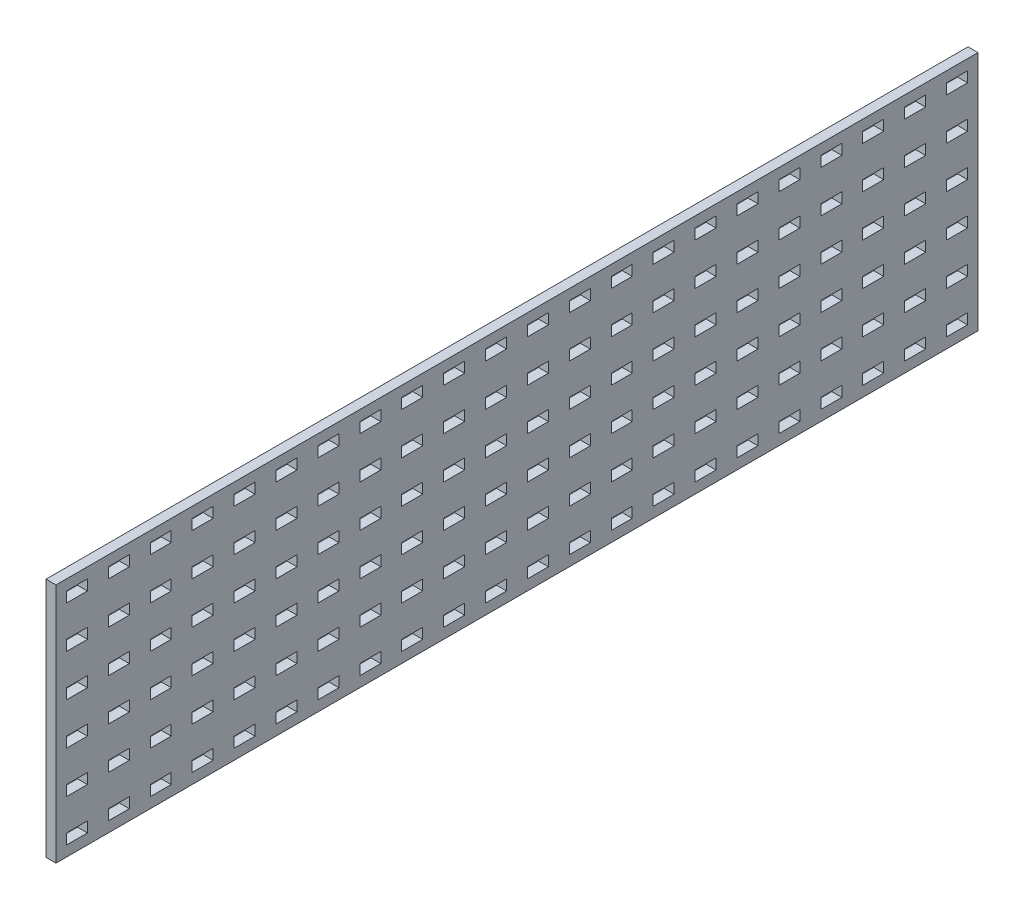
SolidWorks part; units mm, degrees
ref_plane "Front Plane" through (0, 0, 0) normal (0, 0, 1) x (1, 0, 0)
ref_plane "Top Plane" through (0, 0, 0) normal (0, 1, 0) x (1, 0, 0)
ref_plane "Right Plane" through (0, 0, 0) normal (1, 0, 0) x (0, 0, -1)
sketch "Sketch1" plane through (0, 0, 0) normal (1, 0, 0) x (0, 0, -1)
  line L1 (-279.4, -73.025) -> (279.4, -73.025)
  line L2 (-279.4, -73.025) -> (-279.4, 73.025)
  line L3 (-279.4, 73.025) -> (279.4, 73.025)
  line L4 (279.4, -73.025) -> (279.4, 73.025)
  line L5 (-279.4, -73.025) -> (279.4, 73.025) construction
  line L6 (-279.4, 73.025) -> (279.4, -73.025) construction
  point P0 (0, 0)
  dimension "D1" = 558.8
  dimension "D2" = 146.05
extrude "Boss-Extrude1" add sketch "Sketch1" along normal mid plane 6.0452
sketch "Sketch2" plane through (3.0226, 0, 0) normal (1, 0, 0) x (0, 0, -1)
  line L0 (-279.4, -73.025) -> (279.4, -73.025) construction
  line L1 (260.35, -60.325) -> (273.05, -60.325)
  line L2 (260.35, -60.325) -> (260.35, -66.675)
  line L3 (260.35, -66.675) -> (273.05, -66.675)
  line L4 (273.05, -60.325) -> (273.05, -66.675)
  line L5 (260.35, -60.325) -> (273.05, -66.675) construction
  line L6 (260.35, -66.675) -> (273.05, -60.325) construction
  line L7 (279.4, -73.025) -> (279.4, 73.025) construction
  line L8 (234.95, -66.675) -> (247.65, -66.675)
  line L9 (234.95, -60.325) -> (234.95, -66.675)
  line L10 (234.95, -60.325) -> (247.65, -60.325)
  line L11 (247.65, -60.325) -> (247.65, -66.675)
  line L12 (209.55, -66.675) -> (222.25, -66.675)
  line L13 (209.55, -60.325) -> (209.55, -66.675)
  line L14 (209.55, -60.325) -> (222.25, -60.325)
  line L15 (222.25, -60.325) -> (222.25, -66.675)
  line L16 (184.15, -66.675) -> (196.85, -66.675)
  line L17 (184.15, -60.325) -> (184.15, -66.675)
  line L18 (184.15, -60.325) -> (196.85, -60.325)
  line L19 (196.85, -60.325) -> (196.85, -66.675)
  line L20 (158.75, -66.675) -> (171.45, -66.675)
  line L21 (158.75, -60.325) -> (158.75, -66.675)
  line L22 (158.75, -60.325) -> (171.45, -60.325)
  line L23 (171.45, -60.325) -> (171.45, -66.675)
  line L24 (133.35, -66.675) -> (146.05, -66.675)
  line L25 (133.35, -60.325) -> (133.35, -66.675)
  line L26 (133.35, -60.325) -> (146.05, -60.325)
  line L27 (146.05, -60.325) -> (146.05, -66.675)
  line L28 (107.95, -66.675) -> (120.65, -66.675)
  line L29 (107.95, -60.325) -> (107.95, -66.675)
  line L30 (107.95, -60.325) -> (120.65, -60.325)
  line L31 (120.65, -60.325) -> (120.65, -66.675)
  line L32 (82.55, -66.675) -> (95.25, -66.675)
  line L33 (82.55, -60.325) -> (82.55, -66.675)
  line L34 (82.55, -60.325) -> (95.25, -60.325)
  line L35 (95.25, -60.325) -> (95.25, -66.675)
  line L36 (57.15, -66.675) -> (69.85, -66.675)
  line L37 (57.15, -60.325) -> (57.15, -66.675)
  line L38 (57.15, -60.325) -> (69.85, -60.325)
  line L39 (69.85, -60.325) -> (69.85, -66.675)
  line L40 (31.75, -66.675) -> (44.45, -66.675)
  line L41 (31.75, -60.325) -> (31.75, -66.675)
  line L42 (31.75, -60.325) -> (44.45, -60.325)
  line L43 (44.45, -60.325) -> (44.45, -66.675)
  line L44 (6.35, -66.675) -> (19.05, -66.675)
  line L45 (6.35, -60.325) -> (6.35, -66.675)
  line L46 (6.35, -60.325) -> (19.05, -60.325)
  line L47 (19.05, -60.325) -> (19.05, -66.675)
  line L48 (-19.05, -66.675) -> (-6.35, -66.675)
  line L49 (-19.05, -60.325) -> (-19.05, -66.675)
  line L50 (-19.05, -60.325) -> (-6.35, -60.325)
  line L51 (-6.35, -60.325) -> (-6.35, -66.675)
  line L52 (-44.45, -66.675) -> (-31.75, -66.675)
  line L53 (-44.45, -60.325) -> (-44.45, -66.675)
  line L54 (-44.45, -60.325) -> (-31.75, -60.325)
  line L55 (-31.75, -60.325) -> (-31.75, -66.675)
  line L56 (-69.85, -66.675) -> (-57.15, -66.675)
  line L57 (-69.85, -60.325) -> (-69.85, -66.675)
  line L58 (-69.85, -60.325) -> (-57.15, -60.325)
  line L59 (-57.15, -60.325) -> (-57.15, -66.675)
  line L60 (-95.25, -66.675) -> (-82.55, -66.675)
  line L61 (-95.25, -60.325) -> (-95.25, -66.675)
  line L62 (-95.25, -60.325) -> (-82.55, -60.325)
  line L63 (-82.55, -60.325) -> (-82.55, -66.675)
  line L64 (-120.65, -66.675) -> (-107.95, -66.675)
  line L65 (-120.65, -60.325) -> (-120.65, -66.675)
  line L66 (-120.65, -60.325) -> (-107.95, -60.325)
  line L67 (-107.95, -60.325) -> (-107.95, -66.675)
  line L68 (-146.05, -66.675) -> (-133.35, -66.675)
  line L69 (-146.05, -60.325) -> (-146.05, -66.675)
  line L70 (-146.05, -60.325) -> (-133.35, -60.325)
  line L71 (-133.35, -60.325) -> (-133.35, -66.675)
  line L72 (-171.45, -66.675) -> (-158.75, -66.675)
  line L73 (-171.45, -60.325) -> (-171.45, -66.675)
  line L74 (-171.45, -60.325) -> (-158.75, -60.325)
  line L75 (-158.75, -60.325) -> (-158.75, -66.675)
  line L76 (-196.85, -66.675) -> (-184.15, -66.675)
  line L77 (-196.85, -60.325) -> (-196.85, -66.675)
  line L78 (-196.85, -60.325) -> (-184.15, -60.325)
  line L79 (-184.15, -60.325) -> (-184.15, -66.675)
  line L80 (-222.25, -66.675) -> (-209.55, -66.675)
  line L81 (-222.25, -60.325) -> (-222.25, -66.675)
  line L82 (-222.25, -60.325) -> (-209.55, -60.325)
  line L83 (-209.55, -60.325) -> (-209.55, -66.675)
  line L84 (-247.65, -66.675) -> (-234.95, -66.675)
  line L85 (-247.65, -60.325) -> (-247.65, -66.675)
  line L86 (-247.65, -60.325) -> (-234.95, -60.325)
  line L87 (-234.95, -60.325) -> (-234.95, -66.675)
  line L88 (-273.05, -66.675) -> (-260.35, -66.675)
  line L89 (-273.05, -60.325) -> (-273.05, -66.675)
  line L90 (-273.05, -60.325) -> (-260.35, -60.325)
  line L91 (-260.35, -60.325) -> (-260.35, -66.675)
  line L92 (234.95, -41.275) -> (247.65, -41.275)
  line L93 (234.95, -34.925) -> (234.95, -41.275)
  line L94 (234.95, -34.925) -> (247.65, -34.925)
  line L95 (247.65, -34.925) -> (247.65, -41.275)
  line L96 (209.55, -41.275) -> (222.25, -41.275)
  line L97 (209.55, -34.925) -> (209.55, -41.275)
  line L98 (209.55, -34.925) -> (222.25, -34.925)
  line L99 (222.25, -34.925) -> (222.25, -41.275)
  line L100 (184.15, -41.275) -> (196.85, -41.275)
  line L101 (184.15, -34.925) -> (184.15, -41.275)
  line L102 (184.15, -34.925) -> (196.85, -34.925)
  line L103 (196.85, -34.925) -> (196.85, -41.275)
  line L104 (158.75, -41.275) -> (171.45, -41.275)
  line L105 (158.75, -34.925) -> (158.75, -41.275)
  line L106 (158.75, -34.925) -> (171.45, -34.925)
  line L107 (171.45, -34.925) -> (171.45, -41.275)
  line L108 (133.35, -41.275) -> (146.05, -41.275)
  line L109 (133.35, -34.925) -> (133.35, -41.275)
  line L110 (133.35, -34.925) -> (146.05, -34.925)
  line L111 (146.05, -34.925) -> (146.05, -41.275)
  line L112 (107.95, -41.275) -> (120.65, -41.275)
  line L113 (107.95, -34.925) -> (107.95, -41.275)
  line L114 (107.95, -34.925) -> (120.65, -34.925)
  line L115 (120.65, -34.925) -> (120.65, -41.275)
  line L116 (82.55, -41.275) -> (95.25, -41.275)
  line L117 (82.55, -34.925) -> (82.55, -41.275)
  line L118 (82.55, -34.925) -> (95.25, -34.925)
  line L119 (95.25, -34.925) -> (95.25, -41.275)
  line L120 (57.15, -41.275) -> (69.85, -41.275)
  line L121 (57.15, -34.925) -> (57.15, -41.275)
  line L122 (57.15, -34.925) -> (69.85, -34.925)
  line L123 (69.85, -34.925) -> (69.85, -41.275)
  line L124 (31.75, -41.275) -> (44.45, -41.275)
  line L125 (31.75, -34.925) -> (31.75, -41.275)
  line L126 (31.75, -34.925) -> (44.45, -34.925)
  line L127 (44.45, -34.925) -> (44.45, -41.275)
  line L128 (6.35, -41.275) -> (19.05, -41.275)
  line L129 (6.35, -34.925) -> (6.35, -41.275)
  line L130 (6.35, -34.925) -> (19.05, -34.925)
  line L131 (19.05, -34.925) -> (19.05, -41.275)
  line L132 (-19.05, -41.275) -> (-6.35, -41.275)
  line L133 (-19.05, -34.925) -> (-19.05, -41.275)
  line L134 (-19.05, -34.925) -> (-6.35, -34.925)
  line L135 (-6.35, -34.925) -> (-6.35, -41.275)
  line L136 (-44.45, -41.275) -> (-31.75, -41.275)
  line L137 (-44.45, -34.925) -> (-44.45, -41.275)
  line L138 (-44.45, -34.925) -> (-31.75, -34.925)
  line L139 (-31.75, -34.925) -> (-31.75, -41.275)
  line L140 (-69.85, -41.275) -> (-57.15, -41.275)
  line L141 (-69.85, -34.925) -> (-69.85, -41.275)
  line L142 (-69.85, -34.925) -> (-57.15, -34.925)
  line L143 (-57.15, -34.925) -> (-57.15, -41.275)
  line L144 (-95.25, -41.275) -> (-82.55, -41.275)
  line L145 (-95.25, -34.925) -> (-95.25, -41.275)
  line L146 (-95.25, -34.925) -> (-82.55, -34.925)
  line L147 (-82.55, -34.925) -> (-82.55, -41.275)
  line L148 (-120.65, -41.275) -> (-107.95, -41.275)
  line L149 (-120.65, -34.925) -> (-120.65, -41.275)
  line L150 (-120.65, -34.925) -> (-107.95, -34.925)
  line L151 (-107.95, -34.925) -> (-107.95, -41.275)
  line L152 (-146.05, -41.275) -> (-133.35, -41.275)
  line L153 (-146.05, -34.925) -> (-146.05, -41.275)
  line L154 (-146.05, -34.925) -> (-133.35, -34.925)
  line L155 (-133.35, -34.925) -> (-133.35, -41.275)
  line L156 (-171.45, -41.275) -> (-158.75, -41.275)
  line L157 (-171.45, -34.925) -> (-171.45, -41.275)
  line L158 (-171.45, -34.925) -> (-158.75, -34.925)
  line L159 (-158.75, -34.925) -> (-158.75, -41.275)
  line L160 (-196.85, -41.275) -> (-184.15, -41.275)
  line L161 (-196.85, -34.925) -> (-196.85, -41.275)
  line L162 (-196.85, -34.925) -> (-184.15, -34.925)
  line L163 (-184.15, -34.925) -> (-184.15, -41.275)
  line L164 (-222.25, -41.275) -> (-209.55, -41.275)
  line L165 (-222.25, -34.925) -> (-222.25, -41.275)
  line L166 (-222.25, -34.925) -> (-209.55, -34.925)
  line L167 (-209.55, -34.925) -> (-209.55, -41.275)
  line L168 (-247.65, -41.275) -> (-234.95, -41.275)
  line L169 (-247.65, -34.925) -> (-247.65, -41.275)
  line L170 (-247.65, -34.925) -> (-234.95, -34.925)
  line L171 (-234.95, -34.925) -> (-234.95, -41.275)
  line L172 (-273.05, -41.275) -> (-260.35, -41.275)
  line L173 (-273.05, -34.925) -> (-273.05, -41.275)
  line L174 (-273.05, -34.925) -> (-260.35, -34.925)
  line L175 (-260.35, -34.925) -> (-260.35, -41.275)
  line L176 (234.95, -15.875) -> (247.65, -15.875)
  line L177 (234.95, -9.525) -> (234.95, -15.875)
  line L178 (234.95, -9.525) -> (247.65, -9.525)
  line L179 (247.65, -9.525) -> (247.65, -15.875)
  line L180 (209.55, -15.875) -> (222.25, -15.875)
  line L181 (209.55, -9.525) -> (209.55, -15.875)
  line L182 (209.55, -9.525) -> (222.25, -9.525)
  line L183 (222.25, -9.525) -> (222.25, -15.875)
  line L184 (184.15, -15.875) -> (196.85, -15.875)
  line L185 (184.15, -9.525) -> (184.15, -15.875)
  line L186 (184.15, -9.525) -> (196.85, -9.525)
  line L187 (196.85, -9.525) -> (196.85, -15.875)
  line L188 (158.75, -15.875) -> (171.45, -15.875)
  line L189 (158.75, -9.525) -> (158.75, -15.875)
  line L190 (158.75, -9.525) -> (171.45, -9.525)
  line L191 (171.45, -9.525) -> (171.45, -15.875)
  line L192 (133.35, -15.875) -> (146.05, -15.875)
  line L193 (133.35, -9.525) -> (133.35, -15.875)
  line L194 (133.35, -9.525) -> (146.05, -9.525)
  line L195 (146.05, -9.525) -> (146.05, -15.875)
  line L196 (107.95, -15.875) -> (120.65, -15.875)
  line L197 (107.95, -9.525) -> (107.95, -15.875)
  line L198 (107.95, -9.525) -> (120.65, -9.525)
  line L199 (120.65, -9.525) -> (120.65, -15.875)
  line L200 (82.55, -15.875) -> (95.25, -15.875)
  line L201 (82.55, -9.525) -> (82.55, -15.875)
  line L202 (82.55, -9.525) -> (95.25, -9.525)
  line L203 (95.25, -9.525) -> (95.25, -15.875)
  line L204 (57.15, -15.875) -> (69.85, -15.875)
  line L205 (57.15, -9.525) -> (57.15, -15.875)
  line L206 (57.15, -9.525) -> (69.85, -9.525)
  line L207 (69.85, -9.525) -> (69.85, -15.875)
  line L208 (31.75, -15.875) -> (44.45, -15.875)
  line L209 (31.75, -9.525) -> (31.75, -15.875)
  line L210 (31.75, -9.525) -> (44.45, -9.525)
  line L211 (44.45, -9.525) -> (44.45, -15.875)
  line L212 (6.35, -15.875) -> (19.05, -15.875)
  line L213 (6.35, -9.525) -> (6.35, -15.875)
  line L214 (6.35, -9.525) -> (19.05, -9.525)
  line L215 (19.05, -9.525) -> (19.05, -15.875)
  line L216 (-19.05, -15.875) -> (-6.35, -15.875)
  line L217 (-19.05, -9.525) -> (-19.05, -15.875)
  line L218 (-19.05, -9.525) -> (-6.35, -9.525)
  line L219 (-6.35, -9.525) -> (-6.35, -15.875)
  line L220 (-44.45, -15.875) -> (-31.75, -15.875)
  line L221 (-44.45, -9.525) -> (-44.45, -15.875)
  line L222 (-44.45, -9.525) -> (-31.75, -9.525)
  line L223 (-31.75, -9.525) -> (-31.75, -15.875)
  line L224 (-69.85, -15.875) -> (-57.15, -15.875)
  line L225 (-69.85, -9.525) -> (-69.85, -15.875)
  line L226 (-69.85, -9.525) -> (-57.15, -9.525)
  line L227 (-57.15, -9.525) -> (-57.15, -15.875)
  line L228 (-95.25, -15.875) -> (-82.55, -15.875)
  line L229 (-95.25, -9.525) -> (-95.25, -15.875)
  line L230 (-95.25, -9.525) -> (-82.55, -9.525)
  line L231 (-82.55, -9.525) -> (-82.55, -15.875)
  line L232 (-120.65, -15.875) -> (-107.95, -15.875)
  line L233 (-120.65, -9.525) -> (-120.65, -15.875)
  line L234 (-120.65, -9.525) -> (-107.95, -9.525)
  line L235 (-107.95, -9.525) -> (-107.95, -15.875)
  line L236 (-146.05, -15.875) -> (-133.35, -15.875)
  line L237 (-146.05, -9.525) -> (-146.05, -15.875)
  line L238 (-146.05, -9.525) -> (-133.35, -9.525)
  line L239 (-133.35, -9.525) -> (-133.35, -15.875)
  line L240 (-171.45, -15.875) -> (-158.75, -15.875)
  line L241 (-171.45, -9.525) -> (-171.45, -15.875)
  line L242 (-171.45, -9.525) -> (-158.75, -9.525)
  line L243 (-158.75, -9.525) -> (-158.75, -15.875)
  line L244 (-196.85, -15.875) -> (-184.15, -15.875)
  line L245 (-196.85, -9.525) -> (-196.85, -15.875)
  line L246 (-196.85, -9.525) -> (-184.15, -9.525)
  line L247 (-184.15, -9.525) -> (-184.15, -15.875)
  line L248 (-222.25, -15.875) -> (-209.55, -15.875)
  line L249 (-222.25, -9.525) -> (-222.25, -15.875)
  line L250 (-222.25, -9.525) -> (-209.55, -9.525)
  line L251 (-209.55, -9.525) -> (-209.55, -15.875)
  line L252 (-247.65, -15.875) -> (-234.95, -15.875)
  line L253 (-247.65, -9.525) -> (-247.65, -15.875)
  line L254 (-247.65, -9.525) -> (-234.95, -9.525)
  line L255 (-234.95, -9.525) -> (-234.95, -15.875)
  line L256 (-273.05, -15.875) -> (-260.35, -15.875)
  line L257 (-273.05, -9.525) -> (-273.05, -15.875)
  line L258 (-273.05, -9.525) -> (-260.35, -9.525)
  line L259 (-260.35, -9.525) -> (-260.35, -15.875)
  line L260 (234.95, 9.525) -> (247.65, 9.525)
  line L261 (234.95, 15.875) -> (234.95, 9.525)
  line L262 (234.95, 15.875) -> (247.65, 15.875)
  line L263 (247.65, 15.875) -> (247.65, 9.525)
  line L264 (209.55, 9.525) -> (222.25, 9.525)
  line L265 (209.55, 15.875) -> (209.55, 9.525)
  line L266 (209.55, 15.875) -> (222.25, 15.875)
  line L267 (222.25, 15.875) -> (222.25, 9.525)
  line L268 (184.15, 9.525) -> (196.85, 9.525)
  line L269 (184.15, 15.875) -> (184.15, 9.525)
  line L270 (184.15, 15.875) -> (196.85, 15.875)
  line L271 (196.85, 15.875) -> (196.85, 9.525)
  line L272 (158.75, 9.525) -> (171.45, 9.525)
  line L273 (158.75, 15.875) -> (158.75, 9.525)
  line L274 (158.75, 15.875) -> (171.45, 15.875)
  line L275 (171.45, 15.875) -> (171.45, 9.525)
  line L276 (133.35, 9.525) -> (146.05, 9.525)
  line L277 (133.35, 15.875) -> (133.35, 9.525)
  line L278 (133.35, 15.875) -> (146.05, 15.875)
  line L279 (146.05, 15.875) -> (146.05, 9.525)
  line L280 (107.95, 9.525) -> (120.65, 9.525)
  line L281 (107.95, 15.875) -> (107.95, 9.525)
  line L282 (107.95, 15.875) -> (120.65, 15.875)
  line L283 (120.65, 15.875) -> (120.65, 9.525)
  line L284 (82.55, 9.525) -> (95.25, 9.525)
  line L285 (82.55, 15.875) -> (82.55, 9.525)
  line L286 (82.55, 15.875) -> (95.25, 15.875)
  line L287 (95.25, 15.875) -> (95.25, 9.525)
  line L288 (57.15, 9.525) -> (69.85, 9.525)
  line L289 (57.15, 15.875) -> (57.15, 9.525)
  line L290 (57.15, 15.875) -> (69.85, 15.875)
  line L291 (69.85, 15.875) -> (69.85, 9.525)
  line L292 (31.75, 9.525) -> (44.45, 9.525)
  line L293 (31.75, 15.875) -> (31.75, 9.525)
  line L294 (31.75, 15.875) -> (44.45, 15.875)
  line L295 (44.45, 15.875) -> (44.45, 9.525)
  line L296 (6.35, 9.525) -> (19.05, 9.525)
  line L297 (6.35, 15.875) -> (6.35, 9.525)
  line L298 (6.35, 15.875) -> (19.05, 15.875)
  line L299 (19.05, 15.875) -> (19.05, 9.525)
  line L300 (-19.05, 9.525) -> (-6.35, 9.525)
  line L301 (-19.05, 15.875) -> (-19.05, 9.525)
  line L302 (-19.05, 15.875) -> (-6.35, 15.875)
  line L303 (-6.35, 15.875) -> (-6.35, 9.525)
  line L304 (-44.45, 9.525) -> (-31.75, 9.525)
  line L305 (-44.45, 15.875) -> (-44.45, 9.525)
  line L306 (-44.45, 15.875) -> (-31.75, 15.875)
  line L307 (-31.75, 15.875) -> (-31.75, 9.525)
  line L308 (-69.85, 9.525) -> (-57.15, 9.525)
  line L309 (-69.85, 15.875) -> (-69.85, 9.525)
  line L310 (-69.85, 15.875) -> (-57.15, 15.875)
  line L311 (-57.15, 15.875) -> (-57.15, 9.525)
  line L312 (-95.25, 9.525) -> (-82.55, 9.525)
  line L313 (-95.25, 15.875) -> (-95.25, 9.525)
  line L314 (-95.25, 15.875) -> (-82.55, 15.875)
  line L315 (-82.55, 15.875) -> (-82.55, 9.525)
  line L316 (-120.65, 9.525) -> (-107.95, 9.525)
  line L317 (-120.65, 15.875) -> (-120.65, 9.525)
  line L318 (-120.65, 15.875) -> (-107.95, 15.875)
  line L319 (-107.95, 15.875) -> (-107.95, 9.525)
  line L320 (-146.05, 9.525) -> (-133.35, 9.525)
  line L321 (-146.05, 15.875) -> (-146.05, 9.525)
  line L322 (-146.05, 15.875) -> (-133.35, 15.875)
  line L323 (-133.35, 15.875) -> (-133.35, 9.525)
  line L324 (-171.45, 9.525) -> (-158.75, 9.525)
  line L325 (-171.45, 15.875) -> (-171.45, 9.525)
  line L326 (-171.45, 15.875) -> (-158.75, 15.875)
  line L327 (-158.75, 15.875) -> (-158.75, 9.525)
  line L328 (-196.85, 9.525) -> (-184.15, 9.525)
  line L329 (-196.85, 15.875) -> (-196.85, 9.525)
  line L330 (-196.85, 15.875) -> (-184.15, 15.875)
  line L331 (-184.15, 15.875) -> (-184.15, 9.525)
  line L332 (-222.25, 9.525) -> (-209.55, 9.525)
  line L333 (-222.25, 15.875) -> (-222.25, 9.525)
  line L334 (-222.25, 15.875) -> (-209.55, 15.875)
  line L335 (-209.55, 15.875) -> (-209.55, 9.525)
  line L336 (-247.65, 9.525) -> (-234.95, 9.525)
  line L337 (-247.65, 15.875) -> (-247.65, 9.525)
  line L338 (-247.65, 15.875) -> (-234.95, 15.875)
  line L339 (-234.95, 15.875) -> (-234.95, 9.525)
  line L340 (-273.05, 9.525) -> (-260.35, 9.525)
  line L341 (-273.05, 15.875) -> (-273.05, 9.525)
  line L342 (-273.05, 15.875) -> (-260.35, 15.875)
  line L343 (-260.35, 15.875) -> (-260.35, 9.525)
  line L344 (234.95, 34.925) -> (247.65, 34.925)
  line L345 (234.95, 41.275) -> (234.95, 34.925)
  line L346 (234.95, 41.275) -> (247.65, 41.275)
  line L347 (247.65, 41.275) -> (247.65, 34.925)
  line L348 (209.55, 34.925) -> (222.25, 34.925)
  line L349 (209.55, 41.275) -> (209.55, 34.925)
  line L350 (209.55, 41.275) -> (222.25, 41.275)
  line L351 (222.25, 41.275) -> (222.25, 34.925)
  line L352 (184.15, 34.925) -> (196.85, 34.925)
  line L353 (184.15, 41.275) -> (184.15, 34.925)
  line L354 (184.15, 41.275) -> (196.85, 41.275)
  line L355 (196.85, 41.275) -> (196.85, 34.925)
  line L356 (158.75, 34.925) -> (171.45, 34.925)
  line L357 (158.75, 41.275) -> (158.75, 34.925)
  line L358 (158.75, 41.275) -> (171.45, 41.275)
  line L359 (171.45, 41.275) -> (171.45, 34.925)
  line L360 (133.35, 34.925) -> (146.05, 34.925)
  line L361 (133.35, 41.275) -> (133.35, 34.925)
  line L362 (133.35, 41.275) -> (146.05, 41.275)
  line L363 (146.05, 41.275) -> (146.05, 34.925)
  line L364 (107.95, 34.925) -> (120.65, 34.925)
  line L365 (107.95, 41.275) -> (107.95, 34.925)
  line L366 (107.95, 41.275) -> (120.65, 41.275)
  line L367 (120.65, 41.275) -> (120.65, 34.925)
  line L368 (82.55, 34.925) -> (95.25, 34.925)
  line L369 (82.55, 41.275) -> (82.55, 34.925)
  line L370 (82.55, 41.275) -> (95.25, 41.275)
  line L371 (95.25, 41.275) -> (95.25, 34.925)
  line L372 (57.15, 34.925) -> (69.85, 34.925)
  line L373 (57.15, 41.275) -> (57.15, 34.925)
  line L374 (57.15, 41.275) -> (69.85, 41.275)
  line L375 (69.85, 41.275) -> (69.85, 34.925)
  line L376 (31.75, 34.925) -> (44.45, 34.925)
  line L377 (31.75, 41.275) -> (31.75, 34.925)
  line L378 (31.75, 41.275) -> (44.45, 41.275)
  line L379 (44.45, 41.275) -> (44.45, 34.925)
  line L380 (6.35, 34.925) -> (19.05, 34.925)
  line L381 (6.35, 41.275) -> (6.35, 34.925)
  line L382 (6.35, 41.275) -> (19.05, 41.275)
  line L383 (19.05, 41.275) -> (19.05, 34.925)
  line L384 (-19.05, 34.925) -> (-6.35, 34.925)
  line L385 (-19.05, 41.275) -> (-19.05, 34.925)
  line L386 (-19.05, 41.275) -> (-6.35, 41.275)
  line L387 (-6.35, 41.275) -> (-6.35, 34.925)
  line L388 (-44.45, 34.925) -> (-31.75, 34.925)
  line L389 (-44.45, 41.275) -> (-44.45, 34.925)
  line L390 (-44.45, 41.275) -> (-31.75, 41.275)
  line L391 (-31.75, 41.275) -> (-31.75, 34.925)
  line L392 (-69.85, 34.925) -> (-57.15, 34.925)
  line L393 (-69.85, 41.275) -> (-69.85, 34.925)
  line L394 (-69.85, 41.275) -> (-57.15, 41.275)
  line L395 (-57.15, 41.275) -> (-57.15, 34.925)
  line L396 (-95.25, 34.925) -> (-82.55, 34.925)
  line L397 (-95.25, 41.275) -> (-95.25, 34.925)
  line L398 (-95.25, 41.275) -> (-82.55, 41.275)
  line L399 (-82.55, 41.275) -> (-82.55, 34.925)
  line L400 (-120.65, 34.925) -> (-107.95, 34.925)
  line L401 (-120.65, 41.275) -> (-120.65, 34.925)
  line L402 (-120.65, 41.275) -> (-107.95, 41.275)
  line L403 (-107.95, 41.275) -> (-107.95, 34.925)
  line L404 (-146.05, 34.925) -> (-133.35, 34.925)
  line L405 (-146.05, 41.275) -> (-146.05, 34.925)
  line L406 (-146.05, 41.275) -> (-133.35, 41.275)
  line L407 (-133.35, 41.275) -> (-133.35, 34.925)
  line L408 (-171.45, 34.925) -> (-158.75, 34.925)
  line L409 (-171.45, 41.275) -> (-171.45, 34.925)
  line L410 (-171.45, 41.275) -> (-158.75, 41.275)
  line L411 (-158.75, 41.275) -> (-158.75, 34.925)
  line L412 (-196.85, 34.925) -> (-184.15, 34.925)
  line L413 (-196.85, 41.275) -> (-196.85, 34.925)
  line L414 (-196.85, 41.275) -> (-184.15, 41.275)
  line L415 (-184.15, 41.275) -> (-184.15, 34.925)
  line L416 (-222.25, 34.925) -> (-209.55, 34.925)
  line L417 (-222.25, 41.275) -> (-222.25, 34.925)
  line L418 (-222.25, 41.275) -> (-209.55, 41.275)
  line L419 (-209.55, 41.275) -> (-209.55, 34.925)
  line L420 (-247.65, 34.925) -> (-234.95, 34.925)
  line L421 (-247.65, 41.275) -> (-247.65, 34.925)
  line L422 (-247.65, 41.275) -> (-234.95, 41.275)
  line L423 (-234.95, 41.275) -> (-234.95, 34.925)
  line L424 (-273.05, 34.925) -> (-260.35, 34.925)
  line L425 (-273.05, 41.275) -> (-273.05, 34.925)
  line L426 (-273.05, 41.275) -> (-260.35, 41.275)
  line L427 (-260.35, 41.275) -> (-260.35, 34.925)
  line L428 (234.95, 60.325) -> (247.65, 60.325)
  line L429 (234.95, 66.675) -> (234.95, 60.325)
  line L430 (234.95, 66.675) -> (247.65, 66.675)
  line L431 (247.65, 66.675) -> (247.65, 60.325)
  line L432 (209.55, 60.325) -> (222.25, 60.325)
  line L433 (209.55, 66.675) -> (209.55, 60.325)
  line L434 (209.55, 66.675) -> (222.25, 66.675)
  line L435 (222.25, 66.675) -> (222.25, 60.325)
  line L436 (184.15, 60.325) -> (196.85, 60.325)
  line L437 (184.15, 66.675) -> (184.15, 60.325)
  line L438 (184.15, 66.675) -> (196.85, 66.675)
  line L439 (196.85, 66.675) -> (196.85, 60.325)
  line L440 (158.75, 60.325) -> (171.45, 60.325)
  line L441 (158.75, 66.675) -> (158.75, 60.325)
  line L442 (158.75, 66.675) -> (171.45, 66.675)
  line L443 (171.45, 66.675) -> (171.45, 60.325)
  line L444 (133.35, 60.325) -> (146.05, 60.325)
  line L445 (133.35, 66.675) -> (133.35, 60.325)
  line L446 (133.35, 66.675) -> (146.05, 66.675)
  line L447 (146.05, 66.675) -> (146.05, 60.325)
  line L448 (107.95, 60.325) -> (120.65, 60.325)
  line L449 (107.95, 66.675) -> (107.95, 60.325)
  line L450 (107.95, 66.675) -> (120.65, 66.675)
  line L451 (120.65, 66.675) -> (120.65, 60.325)
  line L452 (82.55, 60.325) -> (95.25, 60.325)
  line L453 (82.55, 66.675) -> (82.55, 60.325)
  line L454 (82.55, 66.675) -> (95.25, 66.675)
  line L455 (95.25, 66.675) -> (95.25, 60.325)
  line L456 (57.15, 60.325) -> (69.85, 60.325)
  line L457 (57.15, 66.675) -> (57.15, 60.325)
  line L458 (57.15, 66.675) -> (69.85, 66.675)
  line L459 (69.85, 66.675) -> (69.85, 60.325)
  line L460 (31.75, 60.325) -> (44.45, 60.325)
  line L461 (31.75, 66.675) -> (31.75, 60.325)
  line L462 (31.75, 66.675) -> (44.45, 66.675)
  line L463 (44.45, 66.675) -> (44.45, 60.325)
  line L464 (6.35, 60.325) -> (19.05, 60.325)
  line L465 (6.35, 66.675) -> (6.35, 60.325)
  line L466 (6.35, 66.675) -> (19.05, 66.675)
  line L467 (19.05, 66.675) -> (19.05, 60.325)
  line L468 (-19.05, 60.325) -> (-6.35, 60.325)
  line L469 (-19.05, 66.675) -> (-19.05, 60.325)
  line L470 (-19.05, 66.675) -> (-6.35, 66.675)
  line L471 (-6.35, 66.675) -> (-6.35, 60.325)
  line L472 (-44.45, 60.325) -> (-31.75, 60.325)
  line L473 (-44.45, 66.675) -> (-44.45, 60.325)
  line L474 (-44.45, 66.675) -> (-31.75, 66.675)
  line L475 (-31.75, 66.675) -> (-31.75, 60.325)
  line L476 (-69.85, 60.325) -> (-57.15, 60.325)
  line L477 (-69.85, 66.675) -> (-69.85, 60.325)
  line L478 (-69.85, 66.675) -> (-57.15, 66.675)
  line L479 (-57.15, 66.675) -> (-57.15, 60.325)
  line L480 (-95.25, 60.325) -> (-82.55, 60.325)
  line L481 (-95.25, 66.675) -> (-95.25, 60.325)
  line L482 (-95.25, 66.675) -> (-82.55, 66.675)
  line L483 (-82.55, 66.675) -> (-82.55, 60.325)
  line L484 (-120.65, 60.325) -> (-107.95, 60.325)
  line L485 (-120.65, 66.675) -> (-120.65, 60.325)
  line L486 (-120.65, 66.675) -> (-107.95, 66.675)
  line L487 (-107.95, 66.675) -> (-107.95, 60.325)
  line L488 (-146.05, 60.325) -> (-133.35, 60.325)
  line L489 (-146.05, 66.675) -> (-146.05, 60.325)
  line L490 (-146.05, 66.675) -> (-133.35, 66.675)
  line L491 (-133.35, 66.675) -> (-133.35, 60.325)
  line L492 (-171.45, 60.325) -> (-158.75, 60.325)
  line L493 (-171.45, 66.675) -> (-171.45, 60.325)
  line L494 (-171.45, 66.675) -> (-158.75, 66.675)
  line L495 (-158.75, 66.675) -> (-158.75, 60.325)
  line L496 (-196.85, 60.325) -> (-184.15, 60.325)
  line L497 (-196.85, 66.675) -> (-196.85, 60.325)
  line L498 (-196.85, 66.675) -> (-184.15, 66.675)
  line L499 (-184.15, 66.675) -> (-184.15, 60.325)
  line L500 (-222.25, 60.325) -> (-209.55, 60.325)
  line L501 (-222.25, 66.675) -> (-222.25, 60.325)
  line L502 (-222.25, 66.675) -> (-209.55, 66.675)
  line L503 (-209.55, 66.675) -> (-209.55, 60.325)
  line L504 (-247.65, 60.325) -> (-234.95, 60.325)
  line L505 (-247.65, 66.675) -> (-247.65, 60.325)
  line L506 (-247.65, 66.675) -> (-234.95, 66.675)
  line L507 (-234.95, 66.675) -> (-234.95, 60.325)
  line L508 (-273.05, 60.325) -> (-260.35, 60.325)
  line L509 (-273.05, 66.675) -> (-273.05, 60.325)
  line L510 (-273.05, 66.675) -> (-260.35, 66.675)
  line L511 (-260.35, 66.675) -> (-260.35, 60.325)
  line L512 (234.95, 85.725) -> (247.65, 85.725)
  line L513 (234.95, 92.075) -> (234.95, 85.725)
  line L514 (234.95, 92.075) -> (247.65, 92.075)
  line L515 (247.65, 92.075) -> (247.65, 85.725)
  line L516 (209.55, 85.725) -> (222.25, 85.725)
  line L517 (209.55, 92.075) -> (209.55, 85.725)
  line L518 (209.55, 92.075) -> (222.25, 92.075)
  line L519 (222.25, 92.075) -> (222.25, 85.725)
  line L520 (184.15, 85.725) -> (196.85, 85.725)
  line L521 (184.15, 92.075) -> (184.15, 85.725)
  line L522 (184.15, 92.075) -> (196.85, 92.075)
  line L523 (196.85, 92.075) -> (196.85, 85.725)
  line L524 (158.75, 85.725) -> (171.45, 85.725)
  line L525 (158.75, 92.075) -> (158.75, 85.725)
  line L526 (158.75, 92.075) -> (171.45, 92.075)
  line L527 (171.45, 92.075) -> (171.45, 85.725)
  line L528 (133.35, 85.725) -> (146.05, 85.725)
  line L529 (133.35, 92.075) -> (133.35, 85.725)
  line L530 (133.35, 92.075) -> (146.05, 92.075)
  line L531 (146.05, 92.075) -> (146.05, 85.725)
  line L532 (107.95, 85.725) -> (120.65, 85.725)
  line L533 (107.95, 92.075) -> (107.95, 85.725)
  line L534 (107.95, 92.075) -> (120.65, 92.075)
  line L535 (120.65, 92.075) -> (120.65, 85.725)
  line L536 (82.55, 85.725) -> (95.25, 85.725)
  line L537 (82.55, 92.075) -> (82.55, 85.725)
  line L538 (82.55, 92.075) -> (95.25, 92.075)
  line L539 (95.25, 92.075) -> (95.25, 85.725)
  line L540 (57.15, 85.725) -> (69.85, 85.725)
  line L541 (57.15, 92.075) -> (57.15, 85.725)
  line L542 (57.15, 92.075) -> (69.85, 92.075)
  line L543 (69.85, 92.075) -> (69.85, 85.725)
  line L544 (31.75, 85.725) -> (44.45, 85.725)
  line L545 (31.75, 92.075) -> (31.75, 85.725)
  line L546 (31.75, 92.075) -> (44.45, 92.075)
  line L547 (44.45, 92.075) -> (44.45, 85.725)
  line L548 (6.35, 85.725) -> (19.05, 85.725)
  line L549 (6.35, 92.075) -> (6.35, 85.725)
  line L550 (6.35, 92.075) -> (19.05, 92.075)
  line L551 (19.05, 92.075) -> (19.05, 85.725)
  line L552 (-19.05, 85.725) -> (-6.35, 85.725)
  line L553 (-19.05, 92.075) -> (-19.05, 85.725)
  line L554 (-19.05, 92.075) -> (-6.35, 92.075)
  line L555 (-6.35, 92.075) -> (-6.35, 85.725)
  line L556 (-44.45, 85.725) -> (-31.75, 85.725)
  line L557 (-44.45, 92.075) -> (-44.45, 85.725)
  line L558 (-44.45, 92.075) -> (-31.75, 92.075)
  line L559 (-31.75, 92.075) -> (-31.75, 85.725)
  line L560 (-69.85, 85.725) -> (-57.15, 85.725)
  line L561 (-69.85, 92.075) -> (-69.85, 85.725)
  line L562 (-69.85, 92.075) -> (-57.15, 92.075)
  line L563 (-57.15, 92.075) -> (-57.15, 85.725)
  line L564 (-95.25, 85.725) -> (-82.55, 85.725)
  line L565 (-95.25, 92.075) -> (-95.25, 85.725)
  line L566 (-95.25, 92.075) -> (-82.55, 92.075)
  line L567 (-82.55, 92.075) -> (-82.55, 85.725)
  line L568 (-120.65, 85.725) -> (-107.95, 85.725)
  line L569 (-120.65, 92.075) -> (-120.65, 85.725)
  line L570 (-120.65, 92.075) -> (-107.95, 92.075)
  line L571 (-107.95, 92.075) -> (-107.95, 85.725)
  line L572 (-146.05, 85.725) -> (-133.35, 85.725)
  line L573 (-146.05, 92.075) -> (-146.05, 85.725)
  line L574 (-146.05, 92.075) -> (-133.35, 92.075)
  line L575 (-133.35, 92.075) -> (-133.35, 85.725)
  line L576 (-171.45, 85.725) -> (-158.75, 85.725)
  line L577 (-171.45, 92.075) -> (-171.45, 85.725)
  line L578 (-171.45, 92.075) -> (-158.75, 92.075)
  line L579 (-158.75, 92.075) -> (-158.75, 85.725)
  line L580 (-196.85, 85.725) -> (-184.15, 85.725)
  line L581 (-196.85, 92.075) -> (-196.85, 85.725)
  line L582 (-196.85, 92.075) -> (-184.15, 92.075)
  line L583 (-184.15, 92.075) -> (-184.15, 85.725)
  line L584 (-222.25, 85.725) -> (-209.55, 85.725)
  line L585 (-222.25, 92.075) -> (-222.25, 85.725)
  line L586 (-222.25, 92.075) -> (-209.55, 92.075)
  line L587 (-209.55, 92.075) -> (-209.55, 85.725)
  line L588 (-247.65, 85.725) -> (-234.95, 85.725)
  line L589 (-247.65, 92.075) -> (-247.65, 85.725)
  line L590 (-247.65, 92.075) -> (-234.95, 92.075)
  line L591 (-234.95, 92.075) -> (-234.95, 85.725)
  line L592 (-273.05, 85.725) -> (-260.35, 85.725)
  line L593 (-273.05, 92.075) -> (-273.05, 85.725)
  line L594 (-273.05, 92.075) -> (-260.35, 92.075)
  line L595 (-260.35, 92.075) -> (-260.35, 85.725)
  line L596 (234.95, 111.125) -> (247.65, 111.125)
  line L597 (234.95, 117.475) -> (234.95, 111.125)
  line L598 (234.95, 117.475) -> (247.65, 117.475)
  line L599 (247.65, 117.475) -> (247.65, 111.125)
  line L600 (209.55, 111.125) -> (222.25, 111.125)
  line L601 (209.55, 117.475) -> (209.55, 111.125)
  line L602 (209.55, 117.475) -> (222.25, 117.475)
  line L603 (222.25, 117.475) -> (222.25, 111.125)
  line L604 (184.15, 111.125) -> (196.85, 111.125)
  line L605 (184.15, 117.475) -> (184.15, 111.125)
  line L606 (184.15, 117.475) -> (196.85, 117.475)
  line L607 (196.85, 117.475) -> (196.85, 111.125)
  line L608 (158.75, 111.125) -> (171.45, 111.125)
  line L609 (158.75, 117.475) -> (158.75, 111.125)
  line L610 (158.75, 117.475) -> (171.45, 117.475)
  line L611 (171.45, 117.475) -> (171.45, 111.125)
  line L612 (133.35, 111.125) -> (146.05, 111.125)
  line L613 (133.35, 117.475) -> (133.35, 111.125)
  line L614 (133.35, 117.475) -> (146.05, 117.475)
  line L615 (146.05, 117.475) -> (146.05, 111.125)
  line L616 (107.95, 111.125) -> (120.65, 111.125)
  line L617 (107.95, 117.475) -> (107.95, 111.125)
  line L618 (107.95, 117.475) -> (120.65, 117.475)
  line L619 (120.65, 117.475) -> (120.65, 111.125)
  line L620 (82.55, 111.125) -> (95.25, 111.125)
  line L621 (82.55, 117.475) -> (82.55, 111.125)
  line L622 (82.55, 117.475) -> (95.25, 117.475)
  line L623 (95.25, 117.475) -> (95.25, 111.125)
  line L624 (57.15, 111.125) -> (69.85, 111.125)
  line L625 (57.15, 117.475) -> (57.15, 111.125)
  line L626 (57.15, 117.475) -> (69.85, 117.475)
  line L627 (69.85, 117.475) -> (69.85, 111.125)
  line L628 (31.75, 111.125) -> (44.45, 111.125)
  line L629 (31.75, 117.475) -> (31.75, 111.125)
  line L630 (31.75, 117.475) -> (44.45, 117.475)
  line L631 (44.45, 117.475) -> (44.45, 111.125)
  line L632 (6.35, 111.125) -> (19.05, 111.125)
  line L633 (6.35, 117.475) -> (6.35, 111.125)
  line L634 (6.35, 117.475) -> (19.05, 117.475)
  line L635 (19.05, 117.475) -> (19.05, 111.125)
  line L636 (-19.05, 111.125) -> (-6.35, 111.125)
  line L637 (-19.05, 117.475) -> (-19.05, 111.125)
  line L638 (-19.05, 117.475) -> (-6.35, 117.475)
  line L639 (-6.35, 117.475) -> (-6.35, 111.125)
  line L640 (-44.45, 111.125) -> (-31.75, 111.125)
  line L641 (-44.45, 117.475) -> (-44.45, 111.125)
  line L642 (-44.45, 117.475) -> (-31.75, 117.475)
  line L643 (-31.75, 117.475) -> (-31.75, 111.125)
  line L644 (-69.85, 111.125) -> (-57.15, 111.125)
  line L645 (-69.85, 117.475) -> (-69.85, 111.125)
  line L646 (-69.85, 117.475) -> (-57.15, 117.475)
  line L647 (-57.15, 117.475) -> (-57.15, 111.125)
  line L648 (-95.25, 111.125) -> (-82.55, 111.125)
  line L649 (-95.25, 117.475) -> (-95.25, 111.125)
  line L650 (-95.25, 117.475) -> (-82.55, 117.475)
  line L651 (-82.55, 117.475) -> (-82.55, 111.125)
  line L652 (-120.65, 111.125) -> (-107.95, 111.125)
  line L653 (-120.65, 117.475) -> (-120.65, 111.125)
  line L654 (-120.65, 117.475) -> (-107.95, 117.475)
  line L655 (-107.95, 117.475) -> (-107.95, 111.125)
  line L656 (-146.05, 111.125) -> (-133.35, 111.125)
  line L657 (-146.05, 117.475) -> (-146.05, 111.125)
  line L658 (-146.05, 117.475) -> (-133.35, 117.475)
  line L659 (-133.35, 117.475) -> (-133.35, 111.125)
  line L660 (-171.45, 111.125) -> (-158.75, 111.125)
  line L661 (-171.45, 117.475) -> (-171.45, 111.125)
  line L662 (-171.45, 117.475) -> (-158.75, 117.475)
  line L663 (-158.75, 117.475) -> (-158.75, 111.125)
  line L664 (-196.85, 111.125) -> (-184.15, 111.125)
  line L665 (-196.85, 117.475) -> (-196.85, 111.125)
  line L666 (-196.85, 117.475) -> (-184.15, 117.475)
  line L667 (-184.15, 117.475) -> (-184.15, 111.125)
  line L668 (-222.25, 111.125) -> (-209.55, 111.125)
  line L669 (-222.25, 117.475) -> (-222.25, 111.125)
  line L670 (-222.25, 117.475) -> (-209.55, 117.475)
  line L671 (-209.55, 117.475) -> (-209.55, 111.125)
  line L672 (-247.65, 111.125) -> (-234.95, 111.125)
  line L673 (-247.65, 117.475) -> (-247.65, 111.125)
  line L674 (-247.65, 117.475) -> (-234.95, 117.475)
  line L675 (-234.95, 117.475) -> (-234.95, 111.125)
  line L676 (-273.05, 111.125) -> (-260.35, 111.125)
  line L677 (-273.05, 117.475) -> (-273.05, 111.125)
  line L678 (-273.05, 117.475) -> (-260.35, 117.475)
  line L679 (-260.35, 117.475) -> (-260.35, 111.125)
  line L680 (234.95, 136.525) -> (247.65, 136.525)
  line L681 (234.95, 142.875) -> (234.95, 136.525)
  line L682 (234.95, 142.875) -> (247.65, 142.875)
  line L683 (247.65, 142.875) -> (247.65, 136.525)
  line L684 (209.55, 136.525) -> (222.25, 136.525)
  line L685 (209.55, 142.875) -> (209.55, 136.525)
  line L686 (209.55, 142.875) -> (222.25, 142.875)
  line L687 (222.25, 142.875) -> (222.25, 136.525)
  line L688 (184.15, 136.525) -> (196.85, 136.525)
  line L689 (184.15, 142.875) -> (184.15, 136.525)
  line L690 (184.15, 142.875) -> (196.85, 142.875)
  line L691 (196.85, 142.875) -> (196.85, 136.525)
  line L692 (158.75, 136.525) -> (171.45, 136.525)
  line L693 (158.75, 142.875) -> (158.75, 136.525)
  line L694 (158.75, 142.875) -> (171.45, 142.875)
  line L695 (171.45, 142.875) -> (171.45, 136.525)
  line L696 (133.35, 136.525) -> (146.05, 136.525)
  line L697 (133.35, 142.875) -> (133.35, 136.525)
  line L698 (133.35, 142.875) -> (146.05, 142.875)
  line L699 (146.05, 142.875) -> (146.05, 136.525)
  line L700 (107.95, 136.525) -> (120.65, 136.525)
  line L701 (107.95, 142.875) -> (107.95, 136.525)
  line L702 (107.95, 142.875) -> (120.65, 142.875)
  line L703 (120.65, 142.875) -> (120.65, 136.525)
  line L704 (82.55, 136.525) -> (95.25, 136.525)
  line L705 (82.55, 142.875) -> (82.55, 136.525)
  line L706 (82.55, 142.875) -> (95.25, 142.875)
  line L707 (95.25, 142.875) -> (95.25, 136.525)
  line L708 (57.15, 136.525) -> (69.85, 136.525)
  line L709 (57.15, 142.875) -> (57.15, 136.525)
  line L710 (57.15, 142.875) -> (69.85, 142.875)
  line L711 (69.85, 142.875) -> (69.85, 136.525)
  line L712 (31.75, 136.525) -> (44.45, 136.525)
  line L713 (31.75, 142.875) -> (31.75, 136.525)
  line L714 (31.75, 142.875) -> (44.45, 142.875)
  line L715 (44.45, 142.875) -> (44.45, 136.525)
  line L716 (6.35, 136.525) -> (19.05, 136.525)
  line L717 (6.35, 142.875) -> (6.35, 136.525)
  line L718 (6.35, 142.875) -> (19.05, 142.875)
  line L719 (19.05, 142.875) -> (19.05, 136.525)
  line L720 (-19.05, 136.525) -> (-6.35, 136.525)
  line L721 (-19.05, 142.875) -> (-19.05, 136.525)
  line L722 (-19.05, 142.875) -> (-6.35, 142.875)
  line L723 (-6.35, 142.875) -> (-6.35, 136.525)
  line L724 (-44.45, 136.525) -> (-31.75, 136.525)
  line L725 (-44.45, 142.875) -> (-44.45, 136.525)
  line L726 (-44.45, 142.875) -> (-31.75, 142.875)
  line L727 (-31.75, 142.875) -> (-31.75, 136.525)
  line L728 (-69.85, 136.525) -> (-57.15, 136.525)
  line L729 (-69.85, 142.875) -> (-69.85, 136.525)
  line L730 (-69.85, 142.875) -> (-57.15, 142.875)
  line L731 (-57.15, 142.875) -> (-57.15, 136.525)
  line L732 (-95.25, 136.525) -> (-82.55, 136.525)
  line L733 (-95.25, 142.875) -> (-95.25, 136.525)
  line L734 (-95.25, 142.875) -> (-82.55, 142.875)
  line L735 (-82.55, 142.875) -> (-82.55, 136.525)
  line L736 (-120.65, 136.525) -> (-107.95, 136.525)
  line L737 (-120.65, 142.875) -> (-120.65, 136.525)
  line L738 (-120.65, 142.875) -> (-107.95, 142.875)
  line L739 (-107.95, 142.875) -> (-107.95, 136.525)
  line L740 (-146.05, 136.525) -> (-133.35, 136.525)
  line L741 (-146.05, 142.875) -> (-146.05, 136.525)
  line L742 (-146.05, 142.875) -> (-133.35, 142.875)
  line L743 (-133.35, 142.875) -> (-133.35, 136.525)
  line L744 (-171.45, 136.525) -> (-158.75, 136.525)
  line L745 (-171.45, 142.875) -> (-171.45, 136.525)
  line L746 (-171.45, 142.875) -> (-158.75, 142.875)
  line L747 (-158.75, 142.875) -> (-158.75, 136.525)
  line L748 (-196.85, 136.525) -> (-184.15, 136.525)
  line L749 (-196.85, 142.875) -> (-196.85, 136.525)
  line L750 (-196.85, 142.875) -> (-184.15, 142.875)
  line L751 (-184.15, 142.875) -> (-184.15, 136.525)
  line L752 (-222.25, 136.525) -> (-209.55, 136.525)
  line L753 (-222.25, 142.875) -> (-222.25, 136.525)
  line L754 (-222.25, 142.875) -> (-209.55, 142.875)
  line L755 (-209.55, 142.875) -> (-209.55, 136.525)
  line L756 (-247.65, 136.525) -> (-234.95, 136.525)
  line L757 (-247.65, 142.875) -> (-247.65, 136.525)
  line L758 (-247.65, 142.875) -> (-234.95, 142.875)
  line L759 (-234.95, 142.875) -> (-234.95, 136.525)
  line L760 (-273.05, 136.525) -> (-260.35, 136.525)
  line L761 (-273.05, 142.875) -> (-273.05, 136.525)
  line L762 (-273.05, 142.875) -> (-260.35, 142.875)
  line L763 (-260.35, 142.875) -> (-260.35, 136.525)
  line L764 (234.95, 161.925) -> (247.65, 161.925)
  line L765 (234.95, 168.275) -> (234.95, 161.925)
  line L766 (234.95, 168.275) -> (247.65, 168.275)
  line L767 (247.65, 168.275) -> (247.65, 161.925)
  line L768 (209.55, 161.925) -> (222.25, 161.925)
  line L769 (209.55, 168.275) -> (209.55, 161.925)
  line L770 (209.55, 168.275) -> (222.25, 168.275)
  line L771 (222.25, 168.275) -> (222.25, 161.925)
  line L772 (184.15, 161.925) -> (196.85, 161.925)
  line L773 (184.15, 168.275) -> (184.15, 161.925)
  line L774 (184.15, 168.275) -> (196.85, 168.275)
  line L775 (196.85, 168.275) -> (196.85, 161.925)
  line L776 (158.75, 161.925) -> (171.45, 161.925)
  line L777 (158.75, 168.275) -> (158.75, 161.925)
  line L778 (158.75, 168.275) -> (171.45, 168.275)
  line L779 (171.45, 168.275) -> (171.45, 161.925)
  line L780 (133.35, 161.925) -> (146.05, 161.925)
  line L781 (133.35, 168.275) -> (133.35, 161.925)
  line L782 (133.35, 168.275) -> (146.05, 168.275)
  line L783 (146.05, 168.275) -> (146.05, 161.925)
  line L784 (107.95, 161.925) -> (120.65, 161.925)
  line L785 (107.95, 168.275) -> (107.95, 161.925)
  line L786 (107.95, 168.275) -> (120.65, 168.275)
  line L787 (120.65, 168.275) -> (120.65, 161.925)
  line L788 (82.55, 161.925) -> (95.25, 161.925)
  line L789 (82.55, 168.275) -> (82.55, 161.925)
  line L790 (82.55, 168.275) -> (95.25, 168.275)
  line L791 (95.25, 168.275) -> (95.25, 161.925)
  line L792 (57.15, 161.925) -> (69.85, 161.925)
  line L793 (57.15, 168.275) -> (57.15, 161.925)
  line L794 (57.15, 168.275) -> (69.85, 168.275)
  line L795 (69.85, 168.275) -> (69.85, 161.925)
  line L796 (31.75, 161.925) -> (44.45, 161.925)
  line L797 (31.75, 168.275) -> (31.75, 161.925)
  line L798 (31.75, 168.275) -> (44.45, 168.275)
  line L799 (44.45, 168.275) -> (44.45, 161.925)
  line L800 (6.35, 161.925) -> (19.05, 161.925)
  line L801 (6.35, 168.275) -> (6.35, 161.925)
  line L802 (6.35, 168.275) -> (19.05, 168.275)
  line L803 (19.05, 168.275) -> (19.05, 161.925)
  line L804 (-19.05, 161.925) -> (-6.35, 161.925)
  line L805 (-19.05, 168.275) -> (-19.05, 161.925)
  line L806 (-19.05, 168.275) -> (-6.35, 168.275)
  line L807 (-6.35, 168.275) -> (-6.35, 161.925)
  line L808 (-44.45, 161.925) -> (-31.75, 161.925)
  line L809 (-44.45, 168.275) -> (-44.45, 161.925)
  line L810 (-44.45, 168.275) -> (-31.75, 168.275)
  line L811 (-31.75, 168.275) -> (-31.75, 161.925)
  line L812 (-69.85, 161.925) -> (-57.15, 161.925)
  line L813 (-69.85, 168.275) -> (-69.85, 161.925)
  line L814 (-69.85, 168.275) -> (-57.15, 168.275)
  line L815 (-57.15, 168.275) -> (-57.15, 161.925)
  line L816 (-95.25, 161.925) -> (-82.55, 161.925)
  line L817 (-95.25, 168.275) -> (-95.25, 161.925)
  line L818 (-95.25, 168.275) -> (-82.55, 168.275)
  line L819 (-82.55, 168.275) -> (-82.55, 161.925)
  line L820 (-120.65, 161.925) -> (-107.95, 161.925)
  line L821 (-120.65, 168.275) -> (-120.65, 161.925)
  line L822 (-120.65, 168.275) -> (-107.95, 168.275)
  line L823 (-107.95, 168.275) -> (-107.95, 161.925)
  line L824 (-146.05, 161.925) -> (-133.35, 161.925)
  line L825 (-146.05, 168.275) -> (-146.05, 161.925)
  line L826 (-146.05, 168.275) -> (-133.35, 168.275)
  line L827 (-133.35, 168.275) -> (-133.35, 161.925)
  line L828 (-171.45, 161.925) -> (-158.75, 161.925)
  line L829 (-171.45, 168.275) -> (-171.45, 161.925)
  line L830 (-171.45, 168.275) -> (-158.75, 168.275)
  line L831 (-158.75, 168.275) -> (-158.75, 161.925)
  line L832 (-196.85, 161.925) -> (-184.15, 161.925)
  line L833 (-196.85, 168.275) -> (-196.85, 161.925)
  line L834 (-196.85, 168.275) -> (-184.15, 168.275)
  line L835 (-184.15, 168.275) -> (-184.15, 161.925)
  line L836 (-222.25, 161.925) -> (-209.55, 161.925)
  line L837 (-222.25, 168.275) -> (-222.25, 161.925)
  line L838 (-222.25, 168.275) -> (-209.55, 168.275)
  line L839 (-209.55, 168.275) -> (-209.55, 161.925)
  line L840 (-247.65, 161.925) -> (-234.95, 161.925)
  line L841 (-247.65, 168.275) -> (-247.65, 161.925)
  line L842 (-247.65, 168.275) -> (-234.95, 168.275)
  line L843 (-234.95, 168.275) -> (-234.95, 161.925)
  line L844 (-273.05, 161.925) -> (-260.35, 161.925)
  line L845 (-273.05, 168.275) -> (-273.05, 161.925)
  line L846 (-273.05, 168.275) -> (-260.35, 168.275)
  line L847 (-260.35, 168.275) -> (-260.35, 161.925)
  line L848 (260.35, -41.275) -> (273.05, -41.275)
  line L849 (260.35, -34.925) -> (260.35, -41.275)
  line L850 (260.35, -34.925) -> (273.05, -34.925)
  line L851 (273.05, -34.925) -> (273.05, -41.275)
  line L852 (260.35, -15.875) -> (273.05, -15.875)
  line L853 (260.35, -9.525) -> (260.35, -15.875)
  line L854 (260.35, -9.525) -> (273.05, -9.525)
  line L855 (273.05, -9.525) -> (273.05, -15.875)
  line L856 (260.35, 9.525) -> (273.05, 9.525)
  line L857 (260.35, 15.875) -> (260.35, 9.525)
  line L858 (260.35, 15.875) -> (273.05, 15.875)
  line L859 (273.05, 15.875) -> (273.05, 9.525)
  line L860 (260.35, 34.925) -> (273.05, 34.925)
  line L861 (260.35, 41.275) -> (260.35, 34.925)
  line L862 (260.35, 41.275) -> (273.05, 41.275)
  line L863 (273.05, 41.275) -> (273.05, 34.925)
  line L864 (260.35, 60.325) -> (273.05, 60.325)
  line L865 (260.35, 66.675) -> (260.35, 60.325)
  line L866 (260.35, 66.675) -> (273.05, 66.675)
  line L867 (273.05, 66.675) -> (273.05, 60.325)
  line L868 (260.35, 85.725) -> (273.05, 85.725)
  line L869 (260.35, 92.075) -> (260.35, 85.725)
  line L870 (260.35, 92.075) -> (273.05, 92.075)
  line L871 (273.05, 92.075) -> (273.05, 85.725)
  line L872 (260.35, 111.125) -> (273.05, 111.125)
  line L873 (260.35, 117.475) -> (260.35, 111.125)
  line L874 (260.35, 117.475) -> (273.05, 117.475)
  line L875 (273.05, 117.475) -> (273.05, 111.125)
  line L876 (260.35, 136.525) -> (273.05, 136.525)
  line L877 (260.35, 142.875) -> (260.35, 136.525)
  line L878 (260.35, 142.875) -> (273.05, 142.875)
  line L879 (273.05, 142.875) -> (273.05, 136.525)
  line L880 (260.35, 161.925) -> (273.05, 161.925)
  line L881 (260.35, 168.275) -> (260.35, 161.925)
  line L882 (260.35, 168.275) -> (273.05, 168.275)
  line L883 (273.05, 168.275) -> (273.05, 161.925)
  point P0 (266.7, -63.5)
  point P9 (273.05, -63.5)
  dimension "D1" = 6.35
  dimension "D2" = 12.7
  dimension "D3" = 9.525
  dimension "D4" = 12.7
  dimension "D7" = 25.4
  dimension "D8" = 25.4
  dimension "D5" = 22
  dimension "D6" = 10
extrude "Cut-Extrude1" cut sketch "Sketch2" against normal through all
